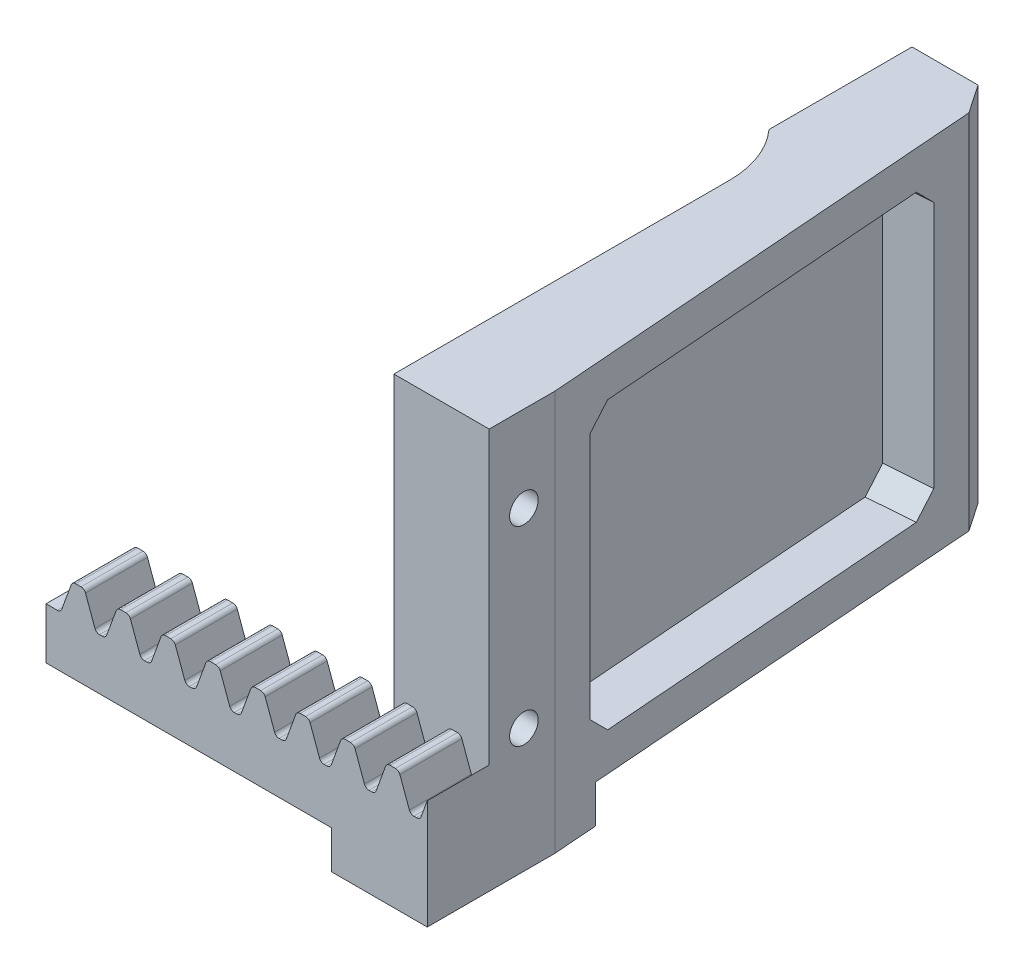
SolidWorks part; units mm, degrees
ref_plane "Front Plane" through (0, 0, 0) normal (0, 0, 1) x (1, 0, 0)
ref_plane "Top Plane" through (0, 0, 0) normal (0, 1, 0) x (1, 0, 0)
ref_plane "Right Plane" through (0, 0, 0) normal (1, 0, 0) x (0, 0, -1)
sketch "Sketch1" plane through (0, 0, 0) normal (0, 0, 1) x (1, 0, 0)
  line L0 (-100, 7.5) -> (-100, -7.5) construction
  line L1 (-100, -7.5) -> (100, -7.5) construction
  line L2 (100, -7.5) -> (100, 7.5) construction
  line L4 (0, 7.5) -> (0, -7.5) construction
  line L5 (-100, 6) -> (100, 6) construction
  line L6 (-97.2361, 7.5) -> (-95.9718, 7.5) construction
  line L7 (-95.9718, 7.5) -> (-94.7434, 4.125) construction
  line L8 (-97.2361, 7.5) -> (-98.4645, 4.125) construction
  line L9 (-98.4645, 4.125) -> (-94.7434, 4.125) construction
  line L10 (-96.604, 7.5) -> (-96.604, 4.125) construction
  line L11 (-100, 0) -> (-87.1792, 0) construction
  line L12 (100, 0) -> (87.1792, 0) construction
  point P15 (-91.8916, 7.5)
  point P16 (-21, -7.5)
  point P17 (-95.4259, 6)
  point P18 (-97.7821, 6)
  point P21 (-0.75, -7.5)
  dimension "Length" = 200
  dimension "Height" = 15
  dimension "Number of Teeth" = 42
  dimension "Pressure Angle" = 20
  dimension "Circular Pitch" = 4.7124
  dimension "Addendum" = 1.5
  dimension "Dedendum" = 1.875
  dimension "Circular Tooth Thickness" = 2.3562
  dimension "Rack Length" = 193.2079
  dimension "D1" = 9.4248
  dimension "For Module" = 1.5
sketch "Sketch2" plane through (0, 0, 0) normal (1, 0, 0) x (0, 0, -1)
  line L0 (-7.5, 0) -> (7.5, 0) construction
  dimension "Face Width" = 15
sketch "Sketch3" plane through (0, 0, 0) normal (0, 0, 1) x (1, 0, 0)
  line L1 (-100, 7.5) -> (100, 7.5)
  line L2 (-100, 7.5) -> (-100, -7.5)
  line L3 (-100, -7.5) -> (100, -7.5)
  line L4 (100, 7.5) -> (100, -7.5)
extrude "Boss-Extrude1" add sketch "Sketch3" against normal up to vertex (7.5 mm away) and the other way up to vertex (7.5 mm away) up to point (0, 0, -7.5) other way up to point (0, 0, 7.5)
sketch "Sketch4" plane through (0, 0, 0) normal (0, 0, 1) x (1, 0, 0)
  line L0 (-96.604, 7.5) -> (-91.8916, 7.5) construction
  line L9 (-94.2478, 7.5) -> (-94.2478, 4.125)
  line L10 (-94.2478, 4.125) -> (-94.7434, 4.125)
  line L11 (-94.7434, 4.125) -> (-95.9718, 7.5)
  line L12 (-95.9718, 7.5) -> (-94.2478, 7.5)
  line L13 (-97.2361, 7.5) -> (-98.4645, 4.125)
  line L14 (-98.4645, 4.125) -> (-98.9602, 4.125)
  line L15 (-98.9602, 4.125) -> (-98.9602, 7.5)
  line L16 (-98.9602, 7.5) -> (-97.2361, 7.5)
extrude "Cut-Extrude1" cut sketch "Sketch4" against normal through all both and the other way through all
fillet "Fillet1" radius 0.5033 4 edges at (-98.4645, 4.125, 0) (-94.7434, 4.125, 0) (-95.9718, 7.5, 0) (-97.2361, 7.5, 0)
pattern_linear "LPattern1" count 42 spacing 4.7124 along (1, 0, 0) of "Cut-Extrude1", "Fillet1"
sketch "Sketch5" plane through (0, 0, 0) normal (0, 0, 1) x (1, 0, 0)
  line L0 (-100, 6) -> (-103.6726, 6) construction
  line L1 (-98.9602, 4.125) -> (-103.6726, 4.125)
  line L2 (-98.9602, 4.125) -> (-98.9602, 7.5)
  line L3 (-98.9602, 7.5) -> (-103.6726, 7.5)
  line L4 (-103.6726, 4.125) -> (-103.6726, 7.5)
  line L5 (98.9602, 7.5) -> (103.6726, 7.5)
  line L6 (98.9602, 7.5) -> (98.9602, 4.125)
  line L7 (98.9602, 4.125) -> (103.6726, 4.125)
  line L8 (103.6726, 7.5) -> (103.6726, 4.125)
  line L9 (103.6726, 6) -> (100, 6) construction
  dimension "D1" = 4.7124
extrude "Cut-Extrude2" cut sketch "Sketch5" against normal through all both and the other way through all
sketch "Sketch6" plane through (0, 0, 0) normal (1, 0, 0) x (0, 0, -1)
  line L0 (-7.5, -7.5) -> (-7.5, 4.125) construction
  line L1 (-1, 10.225) -> (12.8906, 10.225)
  line L2 (-1, 10.225) -> (-1, -11.7256)
  line L3 (-1, -11.7256) -> (12.8906, -11.7256)
  line L4 (12.8906, 10.225) -> (12.8906, -11.7256)
  dimension "D1" = 6.5
extrude "Cut-Extrude3" cut sketch "Sketch6" against normal through all both and the other way through all
sketch "Sketch8" plane through (0, 0, 0) normal (0, 0, 1) x (1, 0, 0)
  line L0 (-100, 4.125) -> (-100, -7.5) construction
  line L1 (-60, 29.716) -> (115.1008, 29.716)
  line L2 (-60, 29.716) -> (-60, -15.2308)
  line L3 (-60, -15.2308) -> (115.1008, -15.2308)
  line L4 (115.1008, 29.716) -> (115.1008, -15.2308)
  dimension "D1" = 40
extrude "Cut-Extrude6" cut sketch "Sketch8" against normal through all and the other way through all
sketch "Sketch9" plane through (0, 0, 0) normal (0, 0, 1) x (1, 0, 0)
  line L0 (-86.8994, 7.5) -> (-87.459, 7.5) construction
  line L1 (-104.5799, -1.25) -> (-49.0781, -1.25)
  line L2 (-104.5799, -1.25) -> (-104.5799, -12.034)
  line L3 (-104.5799, -12.034) -> (-49.0781, -12.034)
  line L4 (-49.0781, -1.25) -> (-49.0781, -12.034)
  dimension "D1" = 8.75
extrude "Cut-Extrude7" cut sketch "Sketch9" along normal through all
sketch "Sketch10" plane through (0, 0, 1) normal (0, 0, -1) x (-1, 0, 0)
  line L1 (60, -1.25) -> (70, -1.25)
  line L2 (60, -1.25) -> (60, 36.75)
  line L3 (60, 36.75) -> (70, 36.75)
  line L4 (70, -1.25) -> (70, 36.75)
  dimension "D1" = 38
  dimension "D2" = 10
extrude "Boss-Extrude2" add sketch "Sketch10" along normal blind 6.9
sketch "Sketch11" plane through (0, 0, -5.9) normal (0, 0, -1) x (-1, 0, 0)
  line L0 (100, -1.25) -> (70, -1.25) construction
  line L1 (60, 36.75) -> (72.54, 36.75)
  line L2 (60, 36.75) -> (60, -1.25)
  line L3 (60, -1.25) -> (72.54, -1.25)
  line L4 (72.54, 36.75) -> (72.54, -1.25)
  dimension "D1" = 12.54
extrude "Boss-Extrude3" add sketch "Sketch11" along normal blind 50
sketch "Sketch12" plane through (0, -1.25, 0) normal (0, -1, 0) x (1, 0, 0)
  line L0 (-60, -55.9) -> (-72.54, -55.9) construction
  line L1 (-72.54, -5.9) -> (-70, -5.9)
  line L2 (-72.54, -5.9) -> (-72.54, -40.9)
  line L3 (-72.54, -40.9) -> (-70, -40.9)
  line L4 (-70, -5.9) -> (-70, -40.9)
  line L5 (-70, -5.9) -> (-70, 1) construction
  line L6 (-60, -5.9) -> (-63.8, -55.9)
  line L7 (-60, 7.5) -> (-60, -55.9) construction
  line L8 (-63.8, -55.9) -> (-60, -55.9)
  line L9 (-60, -55.9) -> (-60, -5.9)
  dimension "D1" = 15
  dimension "D2" = 3.8
extrude "Cut-Extrude8" cut sketch "Sketch12" against normal through all
chamfer "Chamfer1" distance 3 angle 30 1 edges at (-63.8, 17.75, -55.9) first distance on face at (-61.9, 17.75, -30.9)
fillet "Fillet2" radius 10 1 edges at (-70, 17.75, -40.9)
sketch "Sketch13" plane through (-59.2096, 0, 4.4999) normal (0.9971, 0, -0.0758) x (-0.0758, 0, -0.9971)
  line L8 (14.4299, 2.75) -> (53.5741, 2.75)
  line L9 (53.5741, 2.75) -> (53.5741, 32.75)
  line L10 (53.5741, 32.75) -> (14.4299, 32.75)
  line L11 (14.4299, 32.75) -> (14.4299, 2.75)
  line L12 (14.4299, 2.75) -> (53.5741, 2.75)
  line L13 (53.5741, 2.75) -> (53.5741, 32.75)
  line L14 (53.5741, 32.75) -> (14.4299, 32.75)
  line L15 (14.4299, 32.75) -> (14.4299, 2.75)
  dimension "D1" = 4
extrude "Cut-Extrude9" cut sketch "Sketch13" against normal blind 5
chamfer "Chamfer2" distance 2 angle 45 4 edges at (-62.7959, 2.75, -9.699) (-65.7623, 2.75, -48.7307) (-65.7623, 32.75, -48.7307) (-62.7959, 32.75, -9.699)
sketch "Sketch14" plane through (-60, 0, 0) normal (1, 0, 0) x (0, 0, -1)
  line L0 (5.9, 36.75) -> (5.9, -1.25) construction
  line L1 (5.9, 36.75) -> (-1, 36.75) construction
  line L2 (-7.5, -1.25) -> (5.9, -1.25) construction
  circle A0 centre (2.64, 27.75) radius 1.5
  circle A1 centre (2.64, 7.75) radius 1.5
  dimension "D1" = 3
  dimension "D2" = 3.26
  dimension "D3" = 9
  dimension "D4" = 9
  dimension "D5" = 3.26
extrude "Cut-Extrude10" cut sketch "Sketch14" against normal through all
sketch "Sketch15" plane through (0, -1.25, 0) normal (0, -1, 0) x (1, 0, 0)
  line L0 (-70.0697, 7.5) -> (-70, -10.5)
  line L3 (-60, -5.9) -> (-60, 7.5)
  line L4 (-60, 7.5) -> (-60, -5.9) construction
  line L5 (-60, 7.5) -> (-100, 7.5) construction
  line L6 (-60, 7.5) -> (-70.0697, 7.5)
  line L9 (-60, -5.9) -> (-63.5727, -52.9086) construction
  line L10 (-60, -5.9) -> (-60.3496, -10.5)
  line L12 (-70, -10.5) -> (-66.775, -10.5)
  line L13 (-66.775, -10.5) -> (-66.775, 5.1375)
  line L14 (-66.775, 5.1375) -> (-63.575, 5.1375)
  line L15 (-63.575, 5.1375) -> (-63.575, -10.5)
  line L16 (-63.575, -10.5) -> (-60.3496, -10.5)
  line L17 (-70, -34.2405) -> (-70, 1) construction
  point P3 (-70, -10.5)
  point P16 (0, 0)
  dimension "D1" = 18
  dimension "D2" = 3.2
extrude "Boss-Extrude4" add sketch "Sketch15" along normal blind 4 and the other way blind 1
fillet "Fillet3" radius 0.25 2 edges at (-63.575, -3.25, 5.1375) (-66.775, -3.25, 5.1375)
fillet "Fillet4" radius 1 2 edges at (-63.575, -3.25, -10.5) (-66.775, -3.25, -10.5)
equation "\"Diametral Pitch\"= 1 / \"Module\""
equation "\"Pressure Angle\"=20"
equation "\"Dedendum\"= 1.25 / \"Diametral Pitch\""
equation "\"Addendum\"= 1 / \"Diametral Pitch\""
equation "\"WorkingDepth\"= 2 / \"Diametral Pitch\""
equation "\"WholeDepth\"= 2.25 / \"Diametral Pitch\""
equation "\"Clearance\"= 0.25 / \"Diametral Pitch\""
equation "\"ToothThickness\"= ( pi / 2 ) / \"Diametral Pitch\""
equation "\"CircularPitch\"= pi / \"Diametral Pitch\""
equation "\"Fillet\"= \"Clearance\" * cos ( \"Pressure Angle\" ) * tan ( ( 90 + \"Pressure Angle\" ) / 2 )"
equation "\"Module\"= 1.5"
equation "\"Addendum@Sketch1\"=\"Addendum\""
equation "\"Pressure Angle@Sketch1\"=\"Pressure Angle\""
equation "\"Dedendum@Sketch1\"=\"Dedendum\""
equation "\"Circular Pitch@Sketch1\"=\"CircularPitch\""
equation "\"Circular Tooth Thickness@Sketch1\"=\"ToothThickness\""
equation "\"Number of Teeth@Sketch1\"=int(\"Length@Sketch1\"/(2*\"Circular Tooth Thickness@Sketch1\"))"
equation "\"Rack Length@Sketch1\"=\"Circular Pitch@Sketch1\"*(\"Number of Teeth@Sketch1\"-1)"
equation "\"D3@LPattern1\"=\"CircularPitch\""
equation "\"D1@LPattern1\"=\"Number of Teeth@Sketch1\""
equation "\"D1@Sketch1\"=\"Circular Pitch@Sketch1\"*2"
equation "\"D1@Fillet1\"=\"Fillet\""
equation "\"For Module@Sketch1\"=\"Module\""
equation "\"D4@LPattern1\"=\"CircularPitch\""
equation "\"D1@Sketch5\"=\"CircularPitch\""
